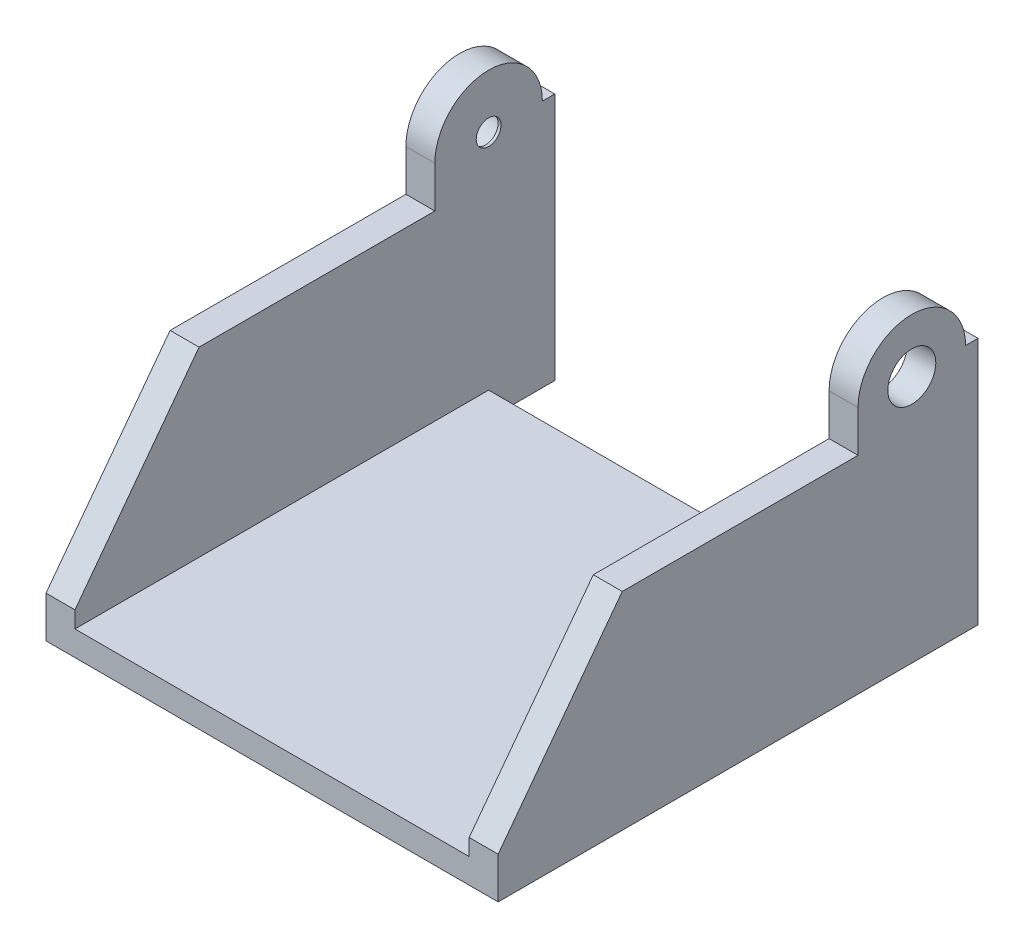
SolidWorks part; units mm, degrees
ref_plane "Front Plane" through (0, 0, 0) normal (0, 0, 1) x (1, 0, 0)
ref_plane "Top Plane" through (0, 0, 0) normal (0, 1, 0) x (1, 0, 0)
ref_plane "Right Plane" through (0, 0, 0) normal (1, 0, 0) x (0, 0, -1)
sketch "Sketch1" plane through (0, 0, 0) normal (0, 0, 1) x (1, 0, 0)
  line L0 (0, 0) -> (-23.825, 0) construction
  line L2 (-23.825, 0) -> (-27.325, 0)
  line L3 (-23.825, 0) -> (-23.825, -30)
  line L4 (-23.825, -30) -> (-27.325, -30)
  line L5 (-27.325, 0) -> (-27.325, -30)
  line L6 (-23.825, -30) -> (0, -30)
  line L7 (-23.825, -30) -> (-23.825, -27)
  line L8 (-23.825, -27) -> (0, -27)
  line L9 (0, -30) -> (0, -27)
  dimension "D1" = 23.825
  dimension "D2" = 3.5
  dimension "D3" = 30
  dimension "D4" = 3
extrude "Boss-Extrude1" add sketch "Sketch1" along normal blind 50 contours L2 L5 L4 L3 | L6 L9 L8 L3 region at (-25.575, -15, 0) region at (-11.9125, -28.5, 0)
sketch "Sketch2" plane through (-23.825, 0, 0) normal (1, 0, 0) x (0, 0, -1)
  line L1 (0, 0) -> (8, 0)
  line L2 (0, 0) -> (0, -30)
  line L3 (0, -30) -> (8, -30)
  line L4 (8, 0) -> (8, -30)
  circle A0 centre (0, 0) radius 1.5
  circle A1 centre (0, 0) radius 6.5
  line M1 (0, -27) -> (0, 0)
  line M2 (0, 0) -> (-50, 0)
  dimension "D1" = 3
  dimension "D2" = 13
  dimension "D3" = 8
extrude "Boss-Extrude2" add sketch "Sketch2" against normal blind 3.5 contours A1 L2 L3 L4 L1 M1 | L2 A1 L1 A0 | L1 A1 A0 M2 region at (-23.825, 2.8781, 0) region at (-23.825, -2.8781, -2.8781) region at (-23.825, -16.9641, -4.1992)
sketch "Sketch3" plane through (-27.325, 0, 0) normal (-1, 0, 0) x (0, 0, 1)
  circle A0 centre (0, 0) radius 1.5
extrude "Cut-Extrude1" cut sketch "Sketch3" against normal through all both and the other way through all
mirror "Mirror1" about plane through (0, 0, 50) normal (-1, 0, 0) of "Cut-Extrude1", "Boss-Extrude2", "Boss-Extrude1"
sketch "Sketch4" plane through (-27.325, 0, 0) normal (-1, 0, 0) x (0, 0, 1)
  circle A0 centre (0, 0) radius 2.5
  dimension "D1" = 5
extrude "Cut-Extrude2" cut sketch "Sketch4" against normal blind 3.15 and the other way through all
sketch "Sketch5" plane through (27.325, 0, 0) normal (1, 0, 0) x (0, 0, -1)
  circle A0 centre (0, 0) radius 2.9
  dimension "D1" = 5.8
extrude "Cut-Extrude3" cut sketch "Sketch5" against normal blind 7.15
sketch "Sketch6" plane through (-27.325, 0, 0) normal (-1, 0, 0) x (0, 0, 1)
  line L1 (50, 0) -> (25, 0)
  line L2 (50, 0) -> (50, -25)
  line L5 (35, -5) -> (50, -25)
  line L7 (6.5, 0) -> (50, 0)
  line L8 (6.5, 0) -> (6.5, -5)
  line L9 (6.5, -5) -> (35, -5)
  line L10 (50, 0) -> (50, -10)
  line M4 (50, 0) -> (6.5, 0)
  line M9 (50, -30) -> (50, 0)
  dimension "D1" = 5
  dimension "D2" = 25
  dimension "D3" = 5
extrude "Cut-Extrude4" cut sketch "Sketch6" against normal blind 7.15 contours L5 M4 M9 region at (-27.325, -5, 49.4983)
ref_plane "Plane1" through (0, 0, 0) normal (1, 0, 0) x (0, 0, -1)
mirror "Mirror2" about plane through (0, 0, 0) normal (1, 0, 0) of "Cut-Extrude4"
